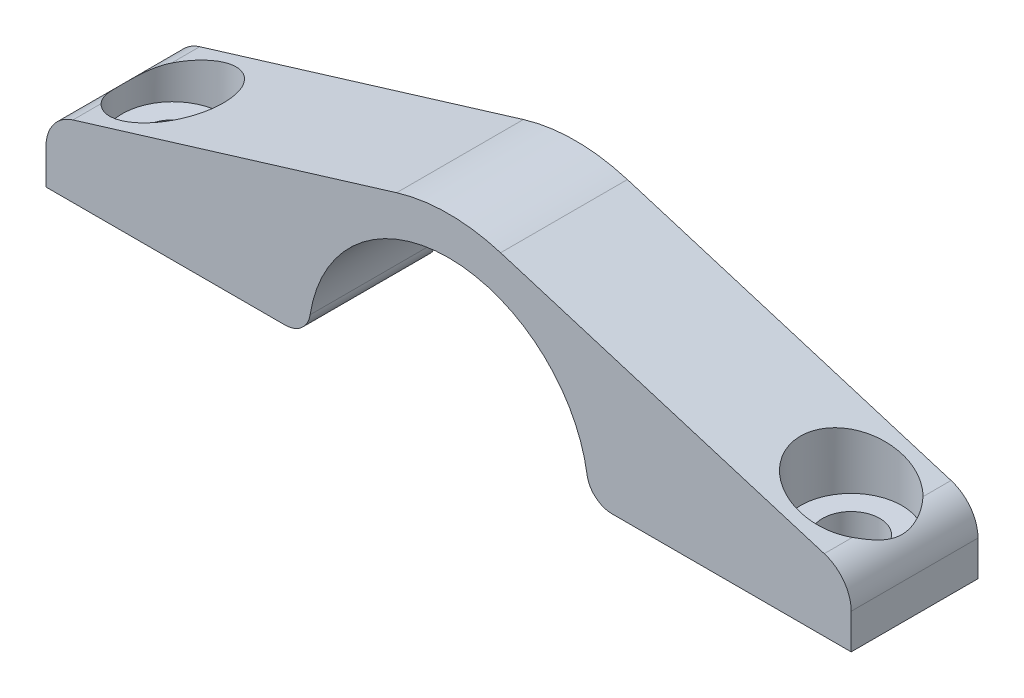
SolidWorks part; units mm, degrees
material "Сплав 2024"
ref_plane "Спереди" through (0, 0, 0) normal (0, 0, 1) x (1, 0, 0)
ref_plane "Сверху" through (0, 0, 0) normal (0, 1, 0) x (1, 0, 0)
ref_plane "Справа" through (0, 0, 0) normal (1, 0, 0) x (0, 0, -1)
sketch "Эскиз1" plane through (0, 0, 0) normal (0, 0, 1) x (1, 0, 0)
  line L0 (-50.7044, 0) -> (94.5195, 0) construction
  line L1 (0, 39.6279) -> (0, -47.9421) construction
  line L2 (-31.75, 5) -> (-4.1012, 13.4381)
  line L4 (-31.75, 5) -> (-31.75, 0)
  line L5 (-31.75, 0) -> (-11.05, 0)
  line L6 (31.75, 5) -> (31.75, 0)
  line L7 (-31.75, 5) -> (17.939, 1.0875) construction
  line L8 (-31.75, 0) -> (31.75, 5) construction
  line L9 (31.75, 5) -> (4.1012, 13.4381)
  line L10 (46.3702, 0) -> (-24.3242, 0) construction
  line L11 (31.75, 0) -> (11.05, 0)
  arc A0 (-11.05, 0) -> (11.05, 0) centre (0, 0) cw
  arc A1 (-4.1012, 13.4381) -> (4.1012, 13.4381) centre (0, 0) cw
  point P10 (0, 2.5)
  dimension "D1" = 11.05
  dimension "D2" = 3
  dimension "D3" = 63.5
  dimension "D4" = 5
  dimension "D5" = 31.75
  dimension "D7" = 5
extrude "Бобышка-Вытянуть1" add sketch "Эскиз1" along normal blind 10
fillet "Скругление1" [suppressed] radius 3
ref_plane "Плоскость1" through (0, 7, 0) normal (0, 1, 0) x (1, 0, 0)
sketch "Эскиз2" plane through (0, 7, 0) normal (0, 1, 0) x (1, 0, 0)
  line L0 (-31.75, -5) -> (-11.05, -5) construction
  line L1 (-31.75, -10) -> (-31.75, 0) construction
  line L2 (-11.05, -10) -> (-11.05, 0) construction
  line L3 (-26.75, -10) -> (-26.75, 0) construction
  dimension "D1" = 5
hole_wizard "Цековка для винта с внутренним шестигранником M42" positions "Эскиз6" profile "Эскиз5" counterbore size "M4" standard "Ansi Metric" end condition through all
sketch "Эскиз6" plane through (0, 7, 0) normal (0, 1, 0) x (1, 0, 0)
  line L0 (-31.75, -5) -> (-11.05, -5) construction
  line L1 (-26.75, -10) -> (-26.75, 0) construction
  point P0 (-26.75, -5)
sketch "Эскиз5" plane through (-26.75, 7, 5) normal (1, 0, 0) x (0, 0, -1)
  line L0 (0, 0) -> (0, 7.05)
  line L1 (0, 7.05) -> (2.25, 7.05)
  line L3 (2.25, 7.05) -> (2.25, 4)
  line L4 (2.25, 4) -> (4, 4)
  line L5 (4, 4) -> (4, 0)
  line L7 (4, 0) -> (0, 0)
  line L11 (0, -6.35) -> (0, 107.95) construction
  dimension "Диаметр сквозного отверстия" = 4.5
  dimension "Глубина сквозного отверстия" = 7.05
  dimension "Диаметр цековки" = 8
  dimension "Глубина цековки" = 4
hole_wizard "Цековка для винта с внутренним шестигранником M43" positions "Эскиз8" profile "Эскиз7" counterbore size "M4" standard "Ansi Metric" end condition through all
sketch "Эскиз8" plane through (0, 7, 0) normal (0, 1, 0) x (1, 0, 0)
  point P0 (-26.75, -5)
sketch "Эскиз7" plane through (-26.75, 7, 5) normal (1, 0, 0) x (0, 0, 1)
  line L0 (0, 0) -> (0, 7)
  line L1 (0, 7) -> (2.25, 7)
  line L3 (2.25, 7) -> (2.25, 4)
  line L4 (2.25, 4) -> (4, 4)
  line L5 (4, 4) -> (4, 0)
  line L7 (4, 0) -> (0, 0)
  line L11 (0, -6.35) -> (0, 107.95) construction
  dimension "Диаметр сквозного отверстия" = 4.5
  dimension "Глубина сквозного отверстия" = 7
  dimension "Диаметр цековки" = 8
  dimension "Глубина цековки" = 4
ref_plane "Плоскость2" through (0, 7, 0) normal (0, -1, 0) x (-1, 0, 0)
sketch "Эскиз9" plane through (0, 7, 0) normal (0, -1, 0) x (-1, 0, 0)
  line L0 (-31.75, -5) -> (-11.05, -5) construction
  line L1 (-31.75, -10) -> (-31.75, 0) construction
  line L2 (-11.05, -10) -> (-11.05, 0) construction
  line L3 (-26.75, 0) -> (-26.75, -10) construction
  dimension "D1" = 5
hole_wizard "Цековка для винта с внутренним шестигранником M44" positions "Эскиз11" profile "Эскиз10" counterbore size "M4" standard "Ansi Metric" end condition through all
sketch "Эскиз11" plane through (0, 7, 0) normal (0, -1, 0) x (-1, 0, 0)
  line L0 (-26.75, 0) -> (-26.75, -10) construction
  line L1 (-31.75, -5) -> (-11.05, -5) construction
  point P0 (-26.75, -5)
sketch "Эскиз10" plane through (26.75, 7, 5) normal (1, 0, 0) x (0, 0, 1)
  line L0 (0, 0) -> (0, 7)
  line L1 (0, 7) -> (2.25, 7)
  line L3 (2.25, 7) -> (2.25, 4)
  line L4 (2.25, 4) -> (4, 4)
  line L5 (4, 4) -> (4, 0)
  line L7 (4, 0) -> (0, 0)
  line L11 (0, -6.35) -> (0, 107.95) construction
  dimension "Диаметр сквозного отверстия" = 4.5
  dimension "Глубина сквозного отверстия" = 7
  dimension "Диаметр цековки" = 8
  dimension "Глубина цековки" = 4
hole_wizard "Цековка для винта с внутренним шестигранником M45" positions "Эскиз13" profile "Эскиз12" counterbore size "M4" standard "Ansi Metric" end condition through all
sketch "Эскиз13" plane through (0, 7, 0) normal (0, -1, 0) x (-1, 0, 0)
  line L0 (-31.75, -5) -> (-11.05, -5) construction
  line L1 (-26.75, 0) -> (-26.75, -10) construction
  point P0 (-26.75, -5)
sketch "Эскиз12" plane through (26.75, 7, 5) normal (1, 0, 0) x (0, 0, -1)
  line L0 (0, 0) -> (0, 7.05)
  line L1 (0, 7.05) -> (2.25, 7.05)
  line L3 (2.25, 7.05) -> (2.25, 4)
  line L4 (2.25, 4) -> (4, 4)
  line L5 (4, 4) -> (4, 0)
  line L7 (4, 0) -> (0, 0)
  line L11 (0, -6.35) -> (0, 107.95) construction
  dimension "Диаметр сквозного отверстия" = 4.5
  dimension "Глубина сквозного отверстия" = 7.05
  dimension "Диаметр цековки" = 8
  dimension "Глубина цековки" = 4
fillet "Скругление4" radius 2 2 edges at (11.05, 0, 5) (-11.05, 0, 5)
fillet "Скругление2" radius 3 2 edges at (-31.75, 5, 5) (31.75, 5, 5)
fillet "Скругление3" [suppressed] radius 0.5
